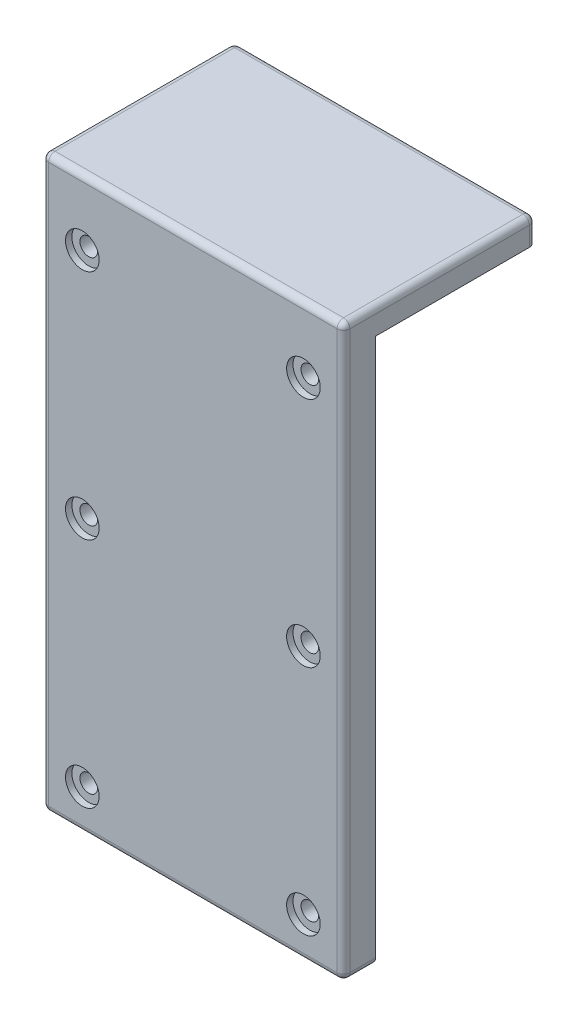
SolidWorks part; units mm, degrees
ref_plane "Front Plane" through (0, 0, 0) normal (0, 0, 1) x (1, 0, 0)
ref_plane "Top Plane" through (0, 0, 0) normal (0, 1, 0) x (1, 0, 0)
ref_plane "Right Plane" through (0, 0, 0) normal (1, 0, 0) x (0, 0, -1)
sketch "Sketch1" plane through (0, 0, 0) normal (0, 0, 1) x (1, 0, 0)
  line L1 (0, 0) -> (94, 0)
  line L2 (0, 0) -> (0, 170)
  line L3 (0, 170) -> (94, 170)
  line L4 (94, 0) -> (94, 170)
  dimension "D1" = 94
  dimension "D2" = 170
extrude "Boss-Extrude1" add sketch "Sketch1" along normal blind 10
sketch "Sketch2" plane through (0, 0, 10) normal (0, 0, 1) x (1, 0, 0)
  line L0 (12.5, 157.5) -> (12.5, 12.5) construction
  line L3 (0, 170) -> (12.5, 170) construction
  line L4 (0, 170) -> (0, 157.5) construction
  line L5 (0, 157.5) -> (12.5, 157.5) construction
  line L7 (12.5, 170) -> (12.5, 157.5) construction
  line L8 (94, 170) -> (81.5, 170) construction
  line L9 (94, 170) -> (94, 157.5) construction
  line L11 (94, 157.5) -> (81.5, 157.5) construction
  line L12 (81.5, 170) -> (81.5, 157.5) construction
  line L13 (0, 0) -> (12.5, 0) construction
  line L14 (0, 0) -> (0, 12.5) construction
  line L15 (0, 12.5) -> (12.5, 12.5) construction
  line L16 (12.5, 0) -> (12.5, 12.5) construction
  line L17 (94, 0) -> (81.5, 0) construction
  line L18 (94, 0) -> (94, 12.5) construction
  line L19 (94, 12.5) -> (81.5, 12.5) construction
  line L20 (81.5, 0) -> (81.5, 12.5) construction
  line L21 (81.5, 157.5) -> (81.5, 12.5) construction
  point P16 (12.5, 85)
  point P17 (12.5, 157.5)
  point P18 (81.5, 85)
  point P19 (12.5, 12.5)
  point P20 (81.5, 12.5)
  point P22 (81.5, 157.5)
  dimension "D1" = 69
hole_wizard "CBORE for M5 SBHCS1" positions "Sketch2" profile "Sketch3" counterbore size "M5" standard "ANSI Metric" end condition through all
sketch "Sketch3" plane through (81.5, 157.5, 10) normal (1, 0, 0) x (0, -1, 0)
  line L0 (0, 0) -> (0, 10)
  line L1 (0, 10) -> (2.75, 10)
  line L3 (2.75, 10) -> (2.75, 2)
  line L4 (2.75, 2) -> (5.25, 2)
  line L5 (5.25, 2) -> (5.25, 0)
  line L7 (5.25, 0) -> (0, 0)
  line L11 (0, -6.35) -> (0, 107.95) construction
  dimension "Thru Hole Dia." = 5.5
  dimension "Thru Hole Depth" = 10
  dimension "C'Bore Dia." = 10.5
  dimension "C'Bore Depth" = 2
sketch "Sketch4" plane through (0, 170, 0) normal (0, 1, 0) x (1, 0, 0)
  line L1 (0, -10) -> (94, -10)
  line L2 (0, -10) -> (0, 50)
  line L3 (0, 50) -> (94, 50)
  line L4 (94, -10) -> (94, 50)
  dimension "D1" = 60
extrude "Boss-Extrude2" add sketch "Sketch4" along normal blind 8
fillet "Fillet1" radius 2 11 edges at (0, 174, -50) (94, 174, -50) (47, 178, -50) (94, 0, 5) (0, 0, 5) (47, 0, 10) (0, 89, 10) (0, 178, -20) (94, 178, -20) (94, 89, 10) (47, 178, 10)
sketch "Sketch5" plane through (0, 0, 0) normal (0, 0, -1) x (-1, 0, 0)
  line L0 (0, 170) -> (0, 2) construction
  line L1 (-52.5, 150) -> (-25.5, 150)
  line L2 (-52.5, 150) -> (-52.5, 143.65)
  line L3 (-52.5, 143.65) -> (-25.5, 143.65)
  line L4 (-25.5, 150) -> (-25.5, 143.65)
  line L5 (-94, 170) -> (0, 170) construction
  line L7 (-25.5, 60.65) -> (-52.5, 60.65)
  line L8 (-25.5, 60.65) -> (-25.5, 54.3)
  line L9 (-25.5, 54.3) -> (-52.5, 54.3)
  line L10 (-52.5, 60.65) -> (-52.5, 54.3)
  dimension "D1" = 6.35
  dimension "D2" = 27
  dimension "D3" = 25.5
  dimension "D4" = 20
  dimension "D5" = 83
extrude "Boss-Extrude3" [suppressed] add sketch "Sketch5" along normal blind 10
sketch "Sketch6" [suppressed] plane through (0, 54.3, 0) normal (0, -1, 0) x (-1, 0, 0)
  line L1 (-52.5, 0) -> (-31.5, 0)
  line L2 (-52.5, 0) -> (-52.5, 3.175)
  line L3 (-52.5, 3.175) -> (-31.5, 3.175)
  line L4 (-31.5, 0) -> (-31.5, 3.175)
  dimension "D1" = 21
  dimension "D2" = 3.175
extrude "Cut-Extrude1" [suppressed] cut sketch "Sketch6" against normal up to surface (95.7 mm away) contours L3 L4 L1 L2
fillet "Fillet2" [suppressed] radius 1.5
chamfer "Chamfer1" [suppressed] distance 5 angle 78
sketch "Sketch9" plane through (0, 0, 0) normal (0, 0, -1) x (-1, 0, 0)
  line L0 (-47, 49) -> (-47, 140) construction
  line L1 (-47, 140) -> (-47, 170) construction
  line L2 (-94, 170) -> (0, 170) construction
  line L5 (-47, 140) -> (-94, 140) construction
  line L6 (-94, 2) -> (-94, 170) construction
  line L8 (-47, 140) -> (0, 140) construction
  line L9 (0, 170) -> (0, 2) construction
  point P0 (-47, 140)
  point P2 (-47, 49)
  dimension "D2" = 30
  dimension "D3" = 91
hole_wizard "M4x0.7 Tapped Hole1" positions "Sketch9" profile "Sketch10" tap size "M4x0.7" standard "ANSI Metric"
sketch "Sketch10" plane through (47, 140, 0) normal (1, 0, 0) x (0, 1, 0)
  line L0 (0, 0) -> (0, 8)
  line L1 (0, 8) -> (1.65, 8)
  line L2 (1.65, 8) -> (1.65, 0)
  line L5 (1.65, 0) -> (0, 0)
  line L10 (0, 8) -> (-1.65, 8) construction
  line L11 (0, -6.35) -> (0, 107.95) construction
  dimension "Tap Drill Dia." = 3.3
  dimension "Tap Drill Depth" = 8
  dimension "Drill Angle" = 180
cosmetic thread "Hole Thread1" parameters "D1"=8, "D2"=4
cosmetic thread "Hole Thread2" parameters "D1"=8, "D2"=4
